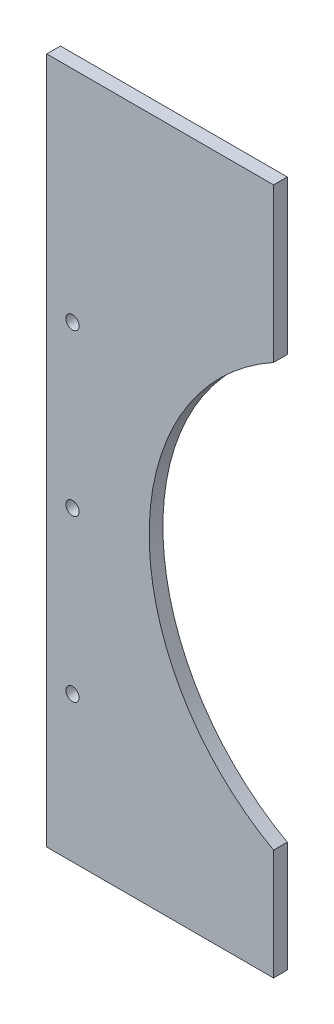
SolidWorks part; units mm, degrees
material "Pine"
ref_plane "Front Plane" through (0, 0, 0) normal (0, 0, 1) x (1, 0, 0)
ref_plane "Top Plane" through (0, 0, 0) normal (0, 1, 0) x (1, 0, 0)
ref_plane "Right Plane" through (0, 0, 0) normal (1, 0, 0) x (0, 0, -1)
sketch "Sketch1" plane through (0, 0, 0) normal (0, 0, 1) x (1, 0, 0)
  line L1 (-43.9944, 113.6168) -> (152.8556, 113.6168)
  line L2 (-43.9944, 113.6168) -> (-43.9944, -482.5212)
  line L3 (-43.9944, -482.5212) -> (152.8556, -482.5212)
  line L4 (152.8556, 113.6168) -> (152.8556, -19.8492)
  line L5 (152.8556, -386.3932) -> (152.8556, -482.5212)
  line L6 (152.8556, -203.1212) -> (254.4556, -203.1212) construction
  arc A0 (152.8556, -19.8492) -> (152.8556, -386.3932) centre (254.4556, -203.1212) ccw
  dimension "D3" = 209.55
  dimension "D1" = 596.138
  dimension "D2" = 196.85
  dimension "D4" = 279.4
  dimension "D5" = 298.45
extrude "Boss-Extrude1" add sketch "Sketch1" along normal blind 11.9062
hole_wizard "29/64 (0.45313) Diameter Hole1" positions "Sketch6" profile "Sketch7" hole size "29/64" standard "ANSI Inch" end condition through all
sketch "Sketch6" plane through (0, 0, 11.9062) normal (0, 0, 1) x (1, 0, 0)
  line L0 (-43.9944, 113.6168) -> (-43.9944, -482.5212) construction
  line L1 (-43.9944, -482.5212) -> (152.8556, -482.5212) construction
  point P0 (-21.6424, -76.8832)
  point P2 (-21.6424, -216.5832)
  point P4 (-21.6424, -356.2832)
  dimension "D1" = 22.352
  dimension "D2" = 126.238
  dimension "D3" = 265.938
  dimension "D4" = 405.638
sketch "Sketch7" plane through (-21.6424, -76.8832, 11.9062) normal (1, 0, 0) x (0, -1, 0)
  line L0 (0, 0) -> (0, 11.9062)
  line L1 (0, 11.9062) -> (5.7548, 11.9062)
  line L2 (5.7548, 11.9062) -> (5.7548, 0)
  line L5 (5.7548, 0) -> (0, 0)
  line L11 (0, -6.35) -> (0, 107.95) construction
  dimension "Thru Hole Dia." = 11.5095
  dimension "Thru Hole Depth" = 11.9062
